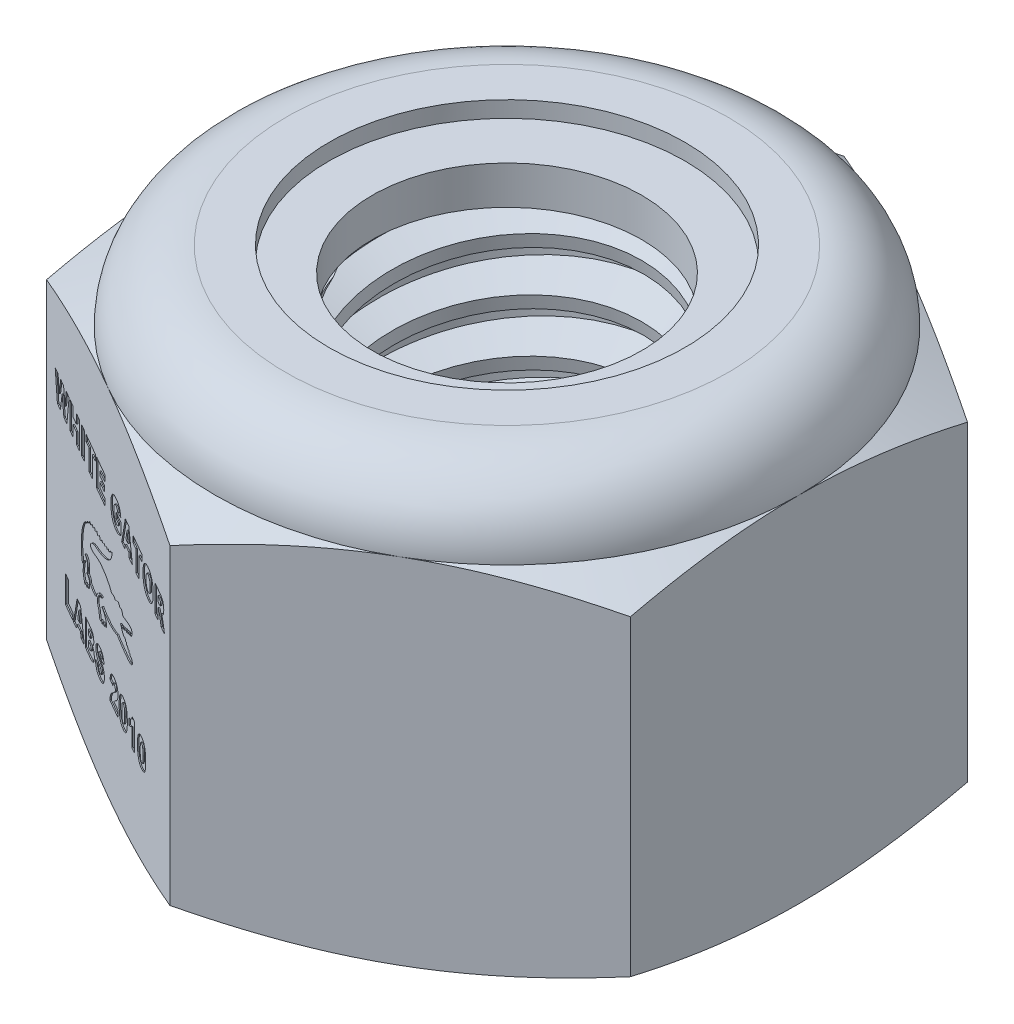
SolidWorks part; units mm, degrees
ref_plane "Front" through (0, 0, 0) normal (0, 0, 1) x (1, 0, 0)
ref_plane "Top" through (0, 0, 0) normal (0, 1, 0) x (1, 0, 0)
ref_plane "Right" through (0, 0, 0) normal (1, 0, 0) x (0, 0, -1)
sketch "Sketch1" plane through (0, 0, 0) normal (0, 1, 0) x (1, 0, 0)
  line L1 (0, 3.1754) -> (-2.75, 1.5877)
  line L2 (-2.75, 1.5877) -> (-2.75, -1.5877)
  line L3 (-2.75, -1.5877) -> (0, -3.1754)
  line L4 (0, -3.1754) -> (2.75, -1.5877)
  line L5 (2.75, -1.5877) -> (2.75, 1.5877)
  line L6 (2.75, 1.5877) -> (0, 3.1754)
  circle A0 centre (0, 0) radius 2.75 construction
  dimension "Hex Flats" = 5.5
extrude "Extrude1" add sketch "Sketch1" along normal blind 4
sketch "Sketch2" plane through (0, 0, 0) normal (1, 0, 0) x (0, 0, -1)
  line L0 (-1.5, 0) -> (-1.5, 4) construction
  line L1 (0, 0) -> (1.5, 0)
  line L2 (0, 0) -> (0, 4)
  line L3 (0, 4) -> (1.5, 4)
  line L4 (1.5, 0) -> (1.5, 4)
  line L5 (-1.5877, 4) -> (1.5877, 4) construction
  line L7 (0, -1.5) -> (0, 0) construction
  dimension "Thread Dia" = 3
revolve "Revolve1" add sketch "Sketch2" angle 360 about L7
sketch "Sketch3" plane through (0, 0, 0) normal (1, 0, 0) x (0, 0, -1)
  line L0 (1.5, 4) -> (-1.5, 4) construction
  line L1 (-1.5, 4) -> (-1.5, 3.5) construction
  line L2 (-1.5, 3.5) -> (1.5, 4) construction
  line L3 (1.5, 4) -> (1.5103, 3.9384) construction
  line L4 (1.5103, 3.9384) -> (1.5822, 3.5068)
  line L5 (1.5822, 3.5068) -> (1.2896, 3.6164)
  line L6 (1.2896, 3.6164) -> (1.269, 3.7397)
  line L7 (1.269, 3.7397) -> (1.5103, 3.9384)
  line L8 (1.2793, 3.6781) -> (1.5462, 3.7226) construction
  line L9 (1.5, 4) -> (1.5, 3.7149) construction
  line L10 (1.5, 3.7149) -> (-1.5, 3.2149) construction
  line L11 (-1.5, 3.2149) -> (-1.5, 3.5) construction
  line L12 (-0.0892, 4) -> (0.0892, 2.9297) construction
  line L13 (-1.5, 0) -> (-1.5, 4) construction
  line L14 (0, 4) -> (1.5, 4) construction
  line L15 (1.5, 0) -> (1.5, 4) construction
  point P13 (0, 3.4649)
  dimension "D1" = 0.0625
  dimension "D2" = 0.125
  dimension "Thread Pitch" = 0.5
  dimension "D4" = 60
  dimension "D5" = 0.5
revolve "Cut-Revolve1" cut sketch "Sketch3" angle 360 about L12
pattern_linear "LPattern1" count 8 spacing 0.5 along (0, -1, 0) count 2 spacing 0.5 along (0, 1, 0) of "Cut-Revolve1"
sketch "Sketch4" plane through (0, 0, 0) normal (1, 0, 0) x (0, 0, -1)
  line L0 (0, 4) -> (1.5, 4)
  line L1 (1.5, 4) -> (1.269, 3.8923)
  line L2 (1.269, 3.8923) -> (1.269, 0.1077)
  line L3 (1.269, 0.1077) -> (1.5, 0)
  line L4 (1.5, 0) -> (0, 0)
  line L5 (0, 0) -> (0, 4)
  line L6 (1.5, 0) -> (1.5, 4) construction
  line L7 (0, 4) -> (1.5, 4) construction
  line L8 (0, 0) -> (1.5, 0) construction
  line L9 (0, 0) -> (0, 4) construction
  line L10 (0, 4) -> (0, 4.2549) construction
  dimension "D1" = 25
revolve "Cut-Revolve2" cut sketch "Sketch4" angle 360 about L10
combine bodies "Combine1" operation type subtract main body 112 bodies to subtract 111
sketch "Sketch5" plane through (0, 0, 0) normal (1, 0, 0) x (0, 0, -1)
  line L0 (0, 0) -> (2.75, 0)
  line L1 (2.75, 0) -> (3.1754, 0.1984)
  line L2 (3.1754, 0.1984) -> (3.1754, 3.135)
  line L3 (3.1754, 3.135) -> (2.75, 3.3333)
  line L4 (2.0833, 4) -> (2.0833, 5.27)
  line L5 (2.0833, 5.27) -> (4.4454, 5.27)
  line L6 (4.4454, 5.27) -> (4.4454, -1.27)
  line L7 (4.4454, -1.27) -> (0, -1.27)
  line L8 (0, -1.27) -> (0, 0)
  line L9 (2.75, 3.3333) -> (2.75, 0) construction
  line L10 (0, 0) -> (1.5, 0) construction
  line L13 (3.1754, 1.6667) -> (4.4454, 1.6667) construction
  line L14 (3.1754, 4) -> (3.1754, 0) construction
  line L15 (0, 0) -> (0, 5.27) construction
  line L20 (0, 5.27) -> (2.0833, 5.27) construction
  line L22 (0, 4) -> (1.5, 4) construction
  arc A0 (2.75, 3.3333) -> (2.0833, 4) centre (2.0833, 3.3333) ccw
  dimension "D1" = 25
  dimension "D2" = 1.27
  dimension "D3" = 4
  dimension "D4" = 0.6667
revolve "Cut-Revolve3" cut sketch "Sketch5" angle 360 about L15
sketch "Sketch6" plane through (0, 0, 0) normal (1, 0, 0) x (0, 0, -1)
  line L0 (0, 3.3333) -> (2.5976, 3.3333)
  line L1 (2.0833, 3.8476) -> (1.6762, 3.8476)
  line L2 (0, 5.27) -> (0, 3.3333)
  line L3 (1.6762, 5.27) -> (0, 5.27)
  line L4 (0, 5.27) -> (2.0833, 5.27) construction
  line L5 (0, 0) -> (0, 5.27) construction
  line L6 (0, 5.27) -> (0, 44.323) construction
  line L7 (1.6762, 3.8476) -> (1.6762, 5.27)
  line L8 (2.0833, 4) -> (2.0833, 3.8476) construction
  line L9 (1.6762, 3.8476) -> (1.269, 3.8476) construction
  line L10 (1.269, 3.8476) -> (1.269, 3.8923) construction
  arc A0 (2.5976, 3.3333) -> (2.0833, 3.8476) centre (2.0833, 3.3333) ccw
  arc A1 (2.75, 3.3333) -> (2.0833, 4) centre (2.0833, 3.3333) ccw construction
  dimension "D1" = 0.1524
revolve "Cut-Revolve4" cut sketch "Sketch6" angle 360 about L6
sketch "Sketch7" plane through (0, 0, 0) normal (1, 0, 0) x (0, 0, -1)
  line L0 (1.269, 3.4095) -> (2.5147, 3.4095)
  line L1 (2.0833, 3.7714) -> (1.269, 3.7714)
  line L2 (1.269, 3.7714) -> (1.269, 3.4095)
  line L3 (1.269, 3.4095) -> (0, 3.4095) construction
  line L4 (0, 3.4095) -> (0, 3.7714) construction
  line L5 (0, 3.7714) -> (1.269, 3.7714) construction
  line L6 (1.269, 3.4095) -> (1.269, 3.3333) construction
  line L7 (0, 3.3333) -> (2.5976, 3.3333) construction
  line L8 (2.0833, 3.7714) -> (2.0833, 3.8476) construction
  arc A0 (2.5147, 3.4095) -> (2.0833, 3.7714) centre (2.0833, 3.3333) ccw
  arc A2 (2.5976, 3.3333) -> (2.0833, 3.8476) centre (2.0833, 3.3333) ccw construction
  dimension "D1" = 0.0762
revolve "Revolve2" add sketch "Sketch7" angle 360 about L4
sketch "Sketch8" plane through (-1.375, 0, 2.3816) normal (-0.5, 0, 0.866) x (0.866, 0, 0.5)
  spline S0 degree 3 poles (0.0913, 2.0614) (0.0849, 2.0435) (0.0556, 2.0479) (0.0369, 2.028) (0.0209, 2.0085) (0.0113, 2.0198) (-0.0003, 2.0262) (-0.0111, 2.0129) (-0.0222, 1.9974) (-0.0368, 2.0082) (-0.0538, 2.0131) (-0.0644, 1.9978) (-0.0784, 1.9851) (-0.0922, 1.9921) (-0.1032, 1.9988) (-0.1122, 1.991) (-0.1216, 1.9855) (-0.1318, 1.9796) (-0.1404, 1.9754) (-0.1472, 1.975) (-0.153, 1.9758) (-0.1547, 1.9806) (-0.1569, 1.9846) (-0.162, 1.985) (-0.1674, 1.9828) (-0.1716, 1.9754) (-0.1794, 1.9665) (-0.1889, 1.9596) (-0.1979, 1.9559) (-0.2029, 1.9559) (-0.2077, 1.9574) (-0.2149, 1.9599) (-0.2175, 1.9685) (-0.2201, 1.9767) (-0.2265, 1.9774) (-0.2297, 1.9736) (-0.2358, 1.9694) (-0.2436, 1.9615) (-0.2537, 1.9546) (-0.2643, 1.9499) (-0.2749, 1.9491) (-0.2823, 1.9559) (-0.2848, 1.9618) (-0.2857, 1.9671) (-0.2894, 1.9681) (-0.2937, 1.9682) (-0.2967, 1.9645) (-0.3072, 1.9553) (-0.3184, 1.9468) (-0.3335, 1.941) (-0.34, 1.9453) (-0.3439, 1.9511) (-0.348, 1.9559) (-0.3543, 1.9583) (-0.3597, 1.9537) (-0.3659, 1.9465) (-0.3738, 1.9384) (-0.3834, 1.9323) (-0.3914, 1.9299) (-0.3992, 1.9317) (-0.4034, 1.9372) (-0.4068, 1.9443) (-0.413, 1.9422) (-0.418, 1.9411) (-0.422, 1.9366) (-0.4315, 1.9263) (-0.4408, 1.9172) (-0.4518, 1.9102) (-0.4548, 1.9117) (-0.4577, 1.9141) (-0.4605, 1.9176) (-0.4636, 1.921) (-0.4666, 1.9248) (-0.4718, 1.9261) (-0.476, 1.9228) (-0.4818, 1.9163) (-0.4901, 1.9058) (-0.5018, 1.8931) (-0.513, 1.8852) (-0.5183, 1.8784) (-0.5224, 1.8784) (-0.5218, 1.881) (-0.5236, 1.8833) (-0.5241, 1.8882) (-0.5323, 1.8872) (-0.5376, 1.8826) (-0.5452, 1.8747) (-0.5554, 1.8647) (-0.566, 1.8511) (-0.5753, 1.8433) (-0.5789, 1.8372) (-0.582, 1.8376) (-0.5834, 1.8399) (-0.5849, 1.8415) (-0.5865, 1.8428) (-0.5888, 1.8426) (-0.5925, 1.8406) (-0.5968, 1.8346) (-0.6109, 1.8249) (-0.619, 1.8122) (-0.6265, 1.8045) knots 0 0 0 0 0.048217 0.074017 0.097146 0.105851 0.117816 0.135226 0.154495 0.169729 0.186348 0.206897 0.224495 0.242122 0.253157 0.262095 0.27718 0.290164 0.300936 0.307749 0.312916 0.318201 0.323368 0.326572 0.333893 0.341326 0.35386 0.37272 0.379457 0.385348 0.388647 0.396148 0.408918 0.416225 0.422134 0.425673 0.432114 0.446566 0.4619 0.47218 0.484819 0.494044 0.502532 0.506729 0.50973 0.514353 0.519954 0.524425 0.560719 0.566271 0.575283 0.583006 0.589877 0.595845 0.602708 0.610899 0.62798 0.639327 0.648132 0.654753 0.663856 0.670956 0.676434 0.682355 0.688018 0.695368 0.72906 0.732221 0.735224 0.739169 0.744684 0.749827 0.75449 0.760478 0.76498 0.771213 0.789299 0.808978 0.827723 0.834537 0.836225 0.838451 0.841007 0.84604 0.851443 0.862598 0.869814 0.88748 0.909678 0.925709 0.928453 0.931263 0.933789 0.936972 0.93865 0.940357 0.943965 0.952208 0.964086 1 1 1 1
  spline S1 degree 3 poles (-0.6265, 1.8045) (-0.6289, 1.7992) (-0.6365, 1.7907) (-0.645, 1.7756) (-0.6546, 1.7589) (-0.6654, 1.7383) (-0.6737, 1.7147) (-0.6804, 1.6901) (-0.686, 1.6694) (-0.6904, 1.6492) (-0.6933, 1.6265) (-0.6939, 1.5954) (-0.6943, 1.5624) (-0.691, 1.5298) (-0.6831, 1.5022) (-0.6732, 1.4798) (-0.6683, 1.4648) (-0.6619, 1.4598) (-0.6573, 1.4618) (-0.6514, 1.4625) (-0.6439, 1.4694) (-0.6381, 1.4794) (-0.6331, 1.4911) (-0.6268, 1.498) (-0.622, 1.5023) (-0.6196, 1.5052) (-0.6166, 1.5053) (-0.617, 1.5014) (-0.62, 1.4987) (-0.6224, 1.4926) (-0.6266, 1.4849) (-0.6314, 1.4718) (-0.6361, 1.4568) (-0.6402, 1.442) (-0.6416, 1.429) (-0.645, 1.4186) (-0.6446, 1.4079) (-0.6451, 1.3975) (-0.6416, 1.3864) (-0.6367, 1.3765) (-0.6316, 1.3658) (-0.6239, 1.3553) (-0.6149, 1.3448) (-0.6084, 1.3339) (-0.6002, 1.3277) (-0.5923, 1.3268) (-0.5872, 1.3312) (-0.5856, 1.3366) (-0.5857, 1.3413) (-0.586, 1.3449) (-0.5848, 1.3481) (-0.5826, 1.3504) (-0.5796, 1.3516) (-0.5762, 1.3511) (-0.5718, 1.3507) (-0.5692, 1.3468) (-0.564, 1.3449) (-0.5598, 1.3405) (-0.553, 1.3365) (-0.5435, 1.3337) (-0.5386, 1.3411) (-0.5334, 1.346) (-0.5322, 1.3536) (-0.5321, 1.3602) (-0.5318, 1.3666) (-0.5278, 1.3699) (-0.5233, 1.3719) (-0.519, 1.3689) (-0.5135, 1.366) (-0.5089, 1.3613) (-0.5024, 1.3575) (-0.4928, 1.3607) (-0.4869, 1.3706) (-0.4793, 1.3855) (-0.4811, 1.4022) (-0.4787, 1.4173) (-0.4829, 1.4265) (-0.4878, 1.4338) (-0.4947, 1.4398) (-0.5026, 1.443) (-0.5102, 1.4474) (-0.5184, 1.4497) (-0.5307, 1.4516) (-0.538, 1.4517) (-0.5468, 1.4511) (-0.5463, 1.4542) (-0.5434, 1.4594) (-0.5377, 1.4692) (-0.5328, 1.4832) (-0.5287, 1.4987) (-0.5272, 1.5172) (-0.5298, 1.5347) (-0.5396, 1.5489) (-0.5501, 1.5583) (-0.5609, 1.5663) (-0.573, 1.5703) (-0.5838, 1.5725) (-0.5898, 1.5734) (-0.5935, 1.5746) (-0.5796, 1.578) (-0.5739, 1.5746) (-0.561, 1.5764) (-0.5542, 1.5742) (-0.5475, 1.5717) (-0.5404, 1.5681) (-0.5344, 1.562) (-0.5275, 1.5549) (-0.5219, 1.5457) (-0.5175, 1.5364) (-0.5152, 1.527) (-0.5129, 1.5172) (-0.513, 1.5059) (-0.513, 1.4941) (-0.5161, 1.4814) (-0.5163, 1.4715) (-0.5214, 1.4635) (-0.5188, 1.4612) (-0.5154, 1.4608) (-0.5095, 1.4595) (-0.5013, 1.4594) (-0.4934, 1.4566) (-0.4858, 1.4553) (-0.4728, 1.4493) (-0.4686, 1.4369) (-0.4669, 1.4264) (-0.4647, 1.4262) (-0.4581, 1.4246) (-0.449, 1.4218) (-0.4386, 1.4196) (-0.4281, 1.4178) (-0.4167, 1.4164) (-0.405, 1.4138) (-0.3956, 1.4128) (-0.3857, 1.4135) (-0.3732, 1.4136) (-0.3597, 1.4138) (-0.3462, 1.4135) (-0.3339, 1.413) (-0.3217, 1.4177) (-0.3094, 1.423) (-0.2961, 1.4361) (-0.294, 1.4501) (-0.2893, 1.4577) knots 0 0 0 0 0.011292 0.0223 0.033937 0.049308 0.06781 0.083097 0.099329 0.110042 0.123747 0.144309 0.171172 0.188484 0.208653 0.227112 0.237112 0.238855 0.242007 0.245967 0.250578 0.261005 0.268815 0.27527 0.279338 0.281421 0.282634 0.283842 0.287544 0.290725 0.296449 0.304901 0.317893 0.327543 0.335024 0.343551 0.348647 0.355939 0.36406 0.371053 0.377797 0.387292 0.3965 0.405032 0.411989 0.416065 0.419424 0.424193 0.426622 0.428837 0.431213 0.433133 0.434832 0.437334 0.43983 0.443124 0.44581 0.450442 0.454609 0.461905 0.465987 0.470748 0.475758 0.480319 0.484232 0.487455 0.490017 0.493236 0.496918 0.50239 0.506103 0.511016 0.520157 0.528136 0.543489 0.552071 0.557352 0.562929 0.569365 0.574847 0.579708 0.586636 0.591433 0.603611 0.604429 0.605144 0.608671 0.61724 0.626494 0.638192 0.648395 0.663163 0.671649 0.681816 0.690801 0.69782 0.706956 0.711272 0.711751 0.712906 0.728184 0.7329 0.736849 0.742242 0.747053 0.752347 0.758799 0.766576 0.773328 0.778941 0.785536 0.79309 0.801066 0.808798 0.818211 0.822204 0.823125 0.824553 0.828768 0.835042 0.840421 0.845231 0.850035 0.867854 0.868398 0.869422 0.871421 0.882677 0.887419 0.892446 0.903561 0.909938 0.916008 0.92211 0.929499 0.940595 0.948448 0.956154 0.964623 0.973682 0.982416 1 1 1 1
  spline S2 degree 3 poles (-0.2893, 1.4577) (-0.2871, 1.46) (-0.2835, 1.4661) (-0.2735, 1.4758) (-0.2602, 1.4855) (-0.2445, 1.4955) (-0.2269, 1.5012) (-0.2109, 1.5064) (-0.1987, 1.5113) (-0.1901, 1.5114) (-0.1836, 1.5135) (-0.1771, 1.5146) (-0.1727, 1.5112) (-0.1724, 1.5067) (-0.1752, 1.5025) (-0.1826, 1.5011) (-0.1912, 1.5018) (-0.2009, 1.4986) (-0.2089, 1.4969) (-0.2227, 1.4921) (-0.238, 1.4846) (-0.2482, 1.4728) (-0.2556, 1.4656) (-0.2626, 1.4562) (-0.2688, 1.4431) (-0.2744, 1.4305) (-0.2734, 1.4211) (-0.2744, 1.4127) (-0.2737, 1.404) (-0.2748, 1.3935) (-0.2683, 1.3869) (-0.2617, 1.381) (-0.2553, 1.3741) (-0.2475, 1.3666) (-0.2408, 1.3591) (-0.2376, 1.3511) (-0.2353, 1.3434) (-0.2315, 1.3346) (-0.2262, 1.3244) (-0.2215, 1.3135) (-0.2177, 1.3045) (-0.2111, 1.3018) (-0.206, 1.3023) (-0.1998, 1.3014) (-0.1926, 1.3051) (-0.1857, 1.3109) (-0.1799, 1.3174) (-0.1784, 1.3233) (-0.1761, 1.3265) (-0.1727, 1.3267) (-0.1697, 1.3225) (-0.1664, 1.3175) (-0.1615, 1.3119) (-0.1571, 1.3073) (-0.1494, 1.3061) (-0.144, 1.3126) (-0.1384, 1.319) (-0.1355, 1.3266) (-0.1314, 1.3324) (-0.1316, 1.3384) (-0.1268, 1.3403) (-0.1245, 1.3355) (-0.1197, 1.332) (-0.1136, 1.3277) (-0.1055, 1.3239) (-0.0931, 1.3229) (-0.0851, 1.3349) (-0.0838, 1.3437) (-0.0841, 1.3496) (-0.0823, 1.3527) (-0.0785, 1.3566) (-0.0729, 1.353) (-0.0697, 1.3487) (-0.0644, 1.346) (-0.0569, 1.3426) (-0.047, 1.3502) (-0.0362, 1.3723) (-0.0546, 1.3952) (-0.0637, 1.4031) knots 0 0 0 0 0.013276 0.02943 0.058363 0.082476 0.107406 0.135768 0.153618 0.161689 0.171706 0.182591 0.187314 0.193219 0.199941 0.206264 0.223753 0.236038 0.248874 0.25808 0.297357 0.318574 0.322951 0.340866 0.367576 0.384252 0.397411 0.406423 0.419884 0.434504 0.448292 0.455948 0.472233 0.48765 0.501621 0.514266 0.523128 0.535517 0.554694 0.571193 0.586429 0.593101 0.599506 0.607865 0.618812 0.631781 0.646414 0.653923 0.657826 0.661848 0.666147 0.678355 0.687637 0.697562 0.704452 0.717194 0.729381 0.74086 0.751176 0.758667 0.763452 0.767118 0.778224 0.788973 0.798202 0.81609 0.83498 0.851289 0.854121 0.859303 0.865993 0.873735 0.882606 0.889168 0.898502 0.91523 0.933533 1 1 1 1
  spline S3 degree 3 poles (-0.0637, 1.4031) (-0.071, 1.4087) (-0.0847, 1.4171) (-0.1056, 1.4262) (-0.1236, 1.4303) (-0.1394, 1.4346) (-0.15, 1.4361) (-0.158, 1.4382) (-0.1594, 1.4448) (-0.1528, 1.4475) (-0.1472, 1.4454) (-0.1373, 1.4439) (-0.1245, 1.4405) (-0.107, 1.4387) (-0.0888, 1.4358) (-0.0623, 1.4351) (-0.017, 1.4359) (0.0538, 1.4356) (0.1427, 1.454) (0.2066, 1.4676) (0.2373, 1.4843) (0.2408, 1.4836) (0.246, 1.4803) (0.2555, 1.4745) (0.2672, 1.4769) (0.2786, 1.4725) (0.2899, 1.4738) (0.3063, 1.4737) (0.3242, 1.4716) (0.3452, 1.4717) (0.3631, 1.472) (0.3829, 1.4694) (0.4062, 1.4704) (0.4447, 1.4698) (0.4825, 1.4705) (0.5171, 1.4696) (0.5484, 1.4731) (0.5729, 1.4759) (0.5891, 1.4821) knots 0 0 0 0 0.031948 0.05562 0.078812 0.095961 0.112076 0.116762 0.123004 0.129426 0.136592 0.143897 0.164038 0.18245 0.204827 0.227975 0.274131 0.362396 0.472777 0.587782 0.58911 0.591037 0.599391 0.610848 0.628309 0.637774 0.65228 0.66699 0.695046 0.714252 0.739998 0.757024 0.783309 0.820706 0.890915 0.91456 0.940428 1 1 1 1
  spline S4 degree 3 poles (0.5891, 1.4821) (0.5983, 1.4845) (0.6092, 1.4913) (0.6208, 1.5033) (0.6206, 1.5111) (0.621, 1.5167) (0.6178, 1.5233) (0.6123, 1.5303) (0.6031, 1.5367) (0.5926, 1.5393) (0.5823, 1.5393) (0.5754, 1.5378) (0.573, 1.5312) (0.5715, 1.5326) (0.5696, 1.5316) (0.5694, 1.5346) (0.5673, 1.5359) (0.5662, 1.5393) (0.5639, 1.543) (0.5616, 1.5469) (0.5587, 1.5496) (0.556, 1.5498) (0.5536, 1.5494) (0.5517, 1.548) (0.55, 1.5459) (0.5471, 1.5454) (0.5455, 1.5428) (0.5425, 1.543) (0.5393, 1.542) (0.5378, 1.5454) (0.536, 1.5478) (0.5343, 1.5503) (0.5328, 1.5527) (0.5312, 1.5549) (0.5301, 1.5584) (0.526, 1.5572) (0.5231, 1.5579) (0.5196, 1.5569) (0.5164, 1.5553) (0.5129, 1.5526) (0.51, 1.5532) (0.5078, 1.5528) (0.5066, 1.5551) (0.5053, 1.5579) (0.5028, 1.5623) (0.4998, 1.5667) (0.4963, 1.5734) (0.4885, 1.5687) (0.485, 1.566) (0.481, 1.5634) knots 0 0 0 0 0.116546 0.171979 0.193509 0.214321 0.242769 0.28328 0.328295 0.381564 0.418486 0.458732 0.472205 0.475171 0.481197 0.492392 0.499562 0.512518 0.53505 0.555738 0.571406 0.581908 0.589881 0.601112 0.612531 0.622685 0.63654 0.645931 0.659362 0.672182 0.686145 0.69901 0.71008 0.722753 0.735214 0.748491 0.766903 0.774853 0.793955 0.813799 0.825742 0.830967 0.839633 0.853705 0.872929 0.901651 0.928936 0.946032 1 1 1 1
  spline S5 degree 3 poles (0.481, 1.5634) (0.4795, 1.5633) (0.4771, 1.5617) (0.4739, 1.5635) (0.4727, 1.5662) (0.4701, 1.5714) (0.4683, 1.5768) (0.4645, 1.5811) (0.4615, 1.5811) (0.4588, 1.5796) (0.4555, 1.5776) (0.4517, 1.5755) (0.4484, 1.5738) (0.4448, 1.5733) (0.4426, 1.5765) (0.4405, 1.5814) (0.4382, 1.5866) (0.4362, 1.5915) (0.4329, 1.594) (0.4303, 1.5923) (0.4274, 1.5909) (0.4226, 1.5879) (0.4136, 1.5853) (0.4024, 1.5853) (0.392, 1.5852) (0.382, 1.588) (0.3724, 1.5938) (0.36, 1.6011) (0.3483, 1.6085) (0.3324, 1.6185) (0.3261, 1.6221) (0.3154, 1.6301) (0.317, 1.6299) (0.3186, 1.63) (0.3274, 1.63) (0.3397, 1.6271) (0.347, 1.6358) (0.3518, 1.6374) (0.3548, 1.6358) (0.3572, 1.6332) (0.3605, 1.631) (0.3633, 1.6283) (0.366, 1.6258) (0.3696, 1.6251) (0.3732, 1.6265) (0.3773, 1.6301) (0.381, 1.6383) (0.3846, 1.6447) (0.3882, 1.6513) (0.3921, 1.6496) (0.3955, 1.6454) (0.4009, 1.6418) (0.4067, 1.6389) (0.4115, 1.6411) (0.4132, 1.646) (0.4153, 1.6511) (0.416, 1.6566) (0.4169, 1.6612) (0.4201, 1.6647) (0.4251, 1.6642) (0.4296, 1.6613) (0.434, 1.6573) (0.4385, 1.6547) (0.4427, 1.651) (0.4486, 1.6558) (0.4481, 1.6609) (0.4493, 1.6642) knots 0 0 0 0 0.01228 0.017915 0.026275 0.034934 0.063098 0.070685 0.076795 0.084706 0.094302 0.106898 0.118255 0.123209 0.133348 0.143983 0.166978 0.17609 0.186449 0.192439 0.198312 0.211604 0.236514 0.269678 0.29806 0.316842 0.350191 0.384057 0.429 0.460133 0.521155 0.52446 0.526804 0.529734 0.538915 0.592764 0.614566 0.621436 0.629926 0.639335 0.649221 0.660155 0.669493 0.677461 0.68716 0.698241 0.719488 0.754519 0.762314 0.769012 0.781857 0.805945 0.819101 0.829391 0.842334 0.858062 0.872694 0.884767 0.894389 0.905805 0.919872 0.936456 0.950947 0.962907 0.972927 1 1 1 1
  spline S6 degree 3 poles (0.4493, 1.6642) (0.4506, 1.6683) (0.4504, 1.6755) (0.4576, 1.6795) (0.4624, 1.6778) (0.4669, 1.674) (0.4715, 1.6706) (0.4773, 1.6653) (0.4839, 1.6737) (0.4851, 1.682) (0.4887, 1.6893) (0.4935, 1.6943) (0.4975, 1.6903) (0.5024, 1.6885) (0.5062, 1.6843) (0.5116, 1.6811) (0.5187, 1.6835) (0.5198, 1.6907) (0.5231, 1.6978) (0.5263, 1.7031) (0.5307, 1.708) (0.5356, 1.7063) (0.5389, 1.7022) (0.5427, 1.698) (0.5495, 1.693) (0.5577, 1.7024) (0.5601, 1.7109) (0.5647, 1.7176) (0.5694, 1.7181) (0.5716, 1.7148) (0.5755, 1.7124) (0.5786, 1.7083) (0.5823, 1.7045) (0.5879, 1.7051) (0.5924, 1.7117) (0.5935, 1.7191) (0.5948, 1.7264) (0.6001, 1.73) (0.6076, 1.7325) (0.6162, 1.742) (0.6156, 1.7561) (0.6078, 1.7656) (0.5986, 1.7713) (0.5884, 1.7749) (0.5789, 1.7744) (0.5698, 1.7745) (0.5615, 1.7745) (0.5521, 1.7739) (0.5436, 1.7718) (0.5345, 1.7701) (0.5258, 1.7675) (0.5161, 1.7657) (0.5064, 1.7643) (0.4973, 1.7613) (0.4861, 1.7591) (0.4779, 1.7562) (0.4723, 1.7551) knots 0 0 0 0 0.032452 0.043005 0.053246 0.066769 0.084815 0.098004 0.11284 0.145121 0.162081 0.173877 0.18503 0.195112 0.212343 0.225207 0.237914 0.259139 0.2723 0.29408 0.30574 0.314199 0.327607 0.342984 0.357158 0.380044 0.412428 0.428075 0.433327 0.443081 0.453195 0.466737 0.480816 0.487976 0.504123 0.532443 0.544592 0.554196 0.576223 0.601695 0.640749 0.665285 0.688092 0.718331 0.741128 0.755919 0.784293 0.800792 0.82413 0.846863 0.867366 0.889975 0.917733 0.938105 0.959048 1 1 1 1
  spline S7 degree 3 poles (0.4723, 1.7551) (0.4667, 1.7541) (0.4579, 1.7517) (0.446, 1.7491) (0.4369, 1.7473) (0.4277, 1.7452) (0.4182, 1.7428) (0.4084, 1.7408) (0.3994, 1.7389) (0.3911, 1.7362) (0.3836, 1.7344) (0.3786, 1.7321) (0.3748, 1.7323) (0.3734, 1.7344) (0.3713, 1.7378) (0.3688, 1.7425) (0.3629, 1.748) (0.3558, 1.7538) (0.3477, 1.7599) (0.3373, 1.7602) (0.3287, 1.7609) (0.3189, 1.757) (0.313, 1.7515) (0.3044, 1.7497) (0.2971, 1.7493) (0.2901, 1.7535) (0.2858, 1.7575) (0.2775, 1.7629) (0.2614, 1.7665) (0.2421, 1.7618) (0.2271, 1.7534) (0.2155, 1.7465) (0.2036, 1.7401) (0.1923, 1.7355) (0.1842, 1.73) (0.1737, 1.7303) (0.1644, 1.7356) (0.1492, 1.7354) (0.1395, 1.7362) (0.1329, 1.7356) knots 0 0 0 0 0.047002 0.074581 0.098698 0.122868 0.151468 0.179139 0.204125 0.22703 0.250435 0.266286 0.272442 0.278681 0.285282 0.306306 0.320615 0.350899 0.38222 0.399602 0.434255 0.451623 0.484206 0.497344 0.522159 0.541774 0.561793 0.570227 0.621862 0.69065 0.727534 0.761683 0.801147 0.83719 0.861929 0.878108 0.919976 0.946367 1 1 1 1
  spline S8 degree 3 poles (0.1329, 1.7356) (0.129, 1.7358) (0.1217, 1.7315) (0.1094, 1.7258) (0.0941, 1.725) (0.0778, 1.7246) (0.0616, 1.7346) (0.0493, 1.7382) (0.0416, 1.7409) knots 0 0 0 0 0.122508 0.251505 0.420804 0.597875 0.74414 1 1 1 1
  spline S9 degree 3 poles (0.0416, 1.7409) (0.0286, 1.746) (0.0117, 1.7476) (-0.0077, 1.7539) (-0.0174, 1.7563) (-0.028, 1.7577) (-0.0391, 1.7598) (-0.051, 1.762) (-0.0689, 1.7647) (-0.0933, 1.7657) (-0.1298, 1.7688) (-0.1671, 1.7667) (-0.1985, 1.7691) (-0.2199, 1.7652) (-0.2373, 1.764) (-0.2571, 1.7617) (-0.2743, 1.7577) (-0.2886, 1.7537) (-0.3011, 1.751) (-0.3148, 1.7468) (-0.3341, 1.7426) (-0.3573, 1.7359) (-0.3779, 1.7323) (-0.4024, 1.7281) (-0.4221, 1.728) (-0.4426, 1.7264) (-0.4522, 1.7313) (-0.4586, 1.7379) (-0.4595, 1.747) (-0.4533, 1.7555) (-0.4402, 1.7687) (-0.421, 1.7834) (-0.397, 1.7939) (-0.377, 1.8048) (-0.3576, 1.8104) (-0.3393, 1.8165) (-0.3187, 1.8206) (-0.295, 1.8264) (-0.2684, 1.8316) (-0.2441, 1.8382) (-0.2178, 1.8463) (-0.1891, 1.8531) (-0.1602, 1.8626) (-0.1323, 1.8718) (-0.0936, 1.8866) (-0.047, 1.9057) (0.0034, 1.9331) (0.0466, 1.962) (0.0768, 1.9958) (0.093, 2.0298) (0.098, 2.0521) (0.0913, 2.0614) knots 0 0 0 0 0.034896 0.042335 0.051393 0.060137 0.069415 0.079869 0.090743 0.114971 0.14154 0.1831 0.209109 0.220295 0.237991 0.25316 0.27044 0.282575 0.290489 0.302931 0.318711 0.340126 0.363845 0.371564 0.402788 0.413927 0.422227 0.429111 0.436434 0.442975 0.454753 0.483686 0.503113 0.520859 0.54098 0.553763 0.569549 0.593837 0.615431 0.637896 0.657454 0.684852 0.7123 0.734326 0.758932 0.816879 0.86128 0.903494 0.947905 0.972512 1 1 1 1
  text T0 "WHITE GATOR \r\n  LABS 2010" font "Arial Black" height in points 1
extrude "Cut-Extrude1" cut sketch "Sketch8" against normal blind 0.01
equation "\"D1@Sketch3\"=\"Thread Pitch@Sketch3\"/8"
equation "\"D2@Sketch3\"=\"Thread Pitch@Sketch3\"/4"
equation "\"D5@Sketch3\"=\"Thread Pitch@Sketch3\""
equation "\"D4@LPattern1\"=\"Thread Pitch@Sketch3\""
equation "\"D3@LPattern1\"=\"Thread Pitch@Sketch3\""
equation "\"D1@LPattern1\"=\"Height@Extrude1\"/\"Thread Pitch@Sketch3\""
equation "\"D4@Sketch5\"=\"Height@Extrude1\"/6"
